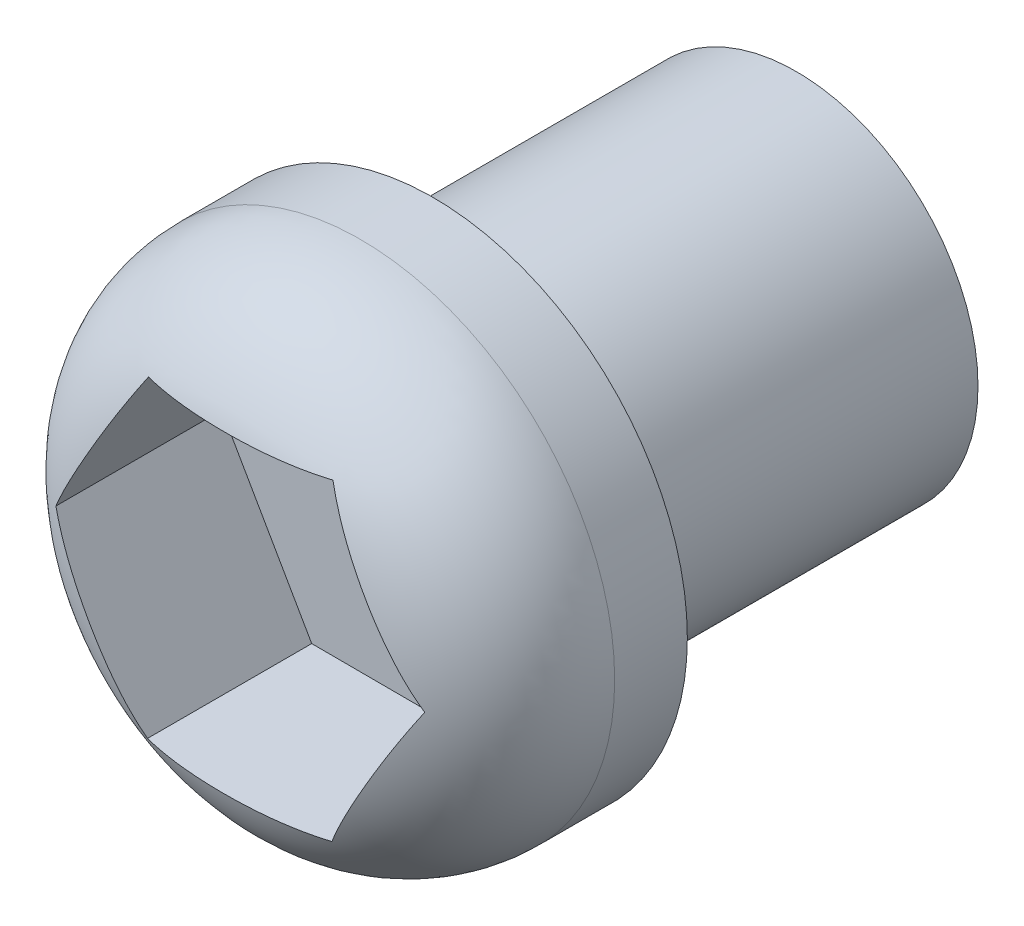
SolidWorks part; units mm, degrees
ref_plane "Front Plane" through (0, 0, 0) normal (0, 0, 1) x (1, 0, 0)
ref_plane "Top Plane" through (0, 0, 0) normal (0, 1, 0) x (1, 0, 0)
ref_plane "Right Plane" through (0, 0, 0) normal (1, 0, 0) x (0, 0, -1)
sketch "Sketch1" plane through (0, 0, 0) normal (0, 0, 1) x (1, 0, 0)
  circle A0 centre (-3.1842, -0.3489) radius 3.5
  dimension "D1" = 7
extrude "Boss-Extrude1" add sketch "Sketch1" along normal blind 3
sketch "Sketch2" plane through (0, 0, 0) normal (0, 0, -1) x (-1, 0, 0)
  circle A0 centre (3.1842, -0.3489) radius 2.5
  dimension "D1" = 5
extrude "Boss-Extrude2" add sketch "Sketch2" along normal blind 5
sketch "Sketch3" plane through (0, 0, 3) normal (0, 0, 1) x (1, 0, 0)
  line L1 (-4.3404, 1.8121) -> (-5.5926, -0.3413)
  line L2 (-5.5926, -0.3413) -> (-4.3537, -2.5024)
  line L3 (-4.3537, -2.5024) -> (-1.8627, -2.51)
  line L4 (-1.8627, -2.51) -> (-0.6106, -0.3566)
  line L5 (-0.6106, -0.3566) -> (-1.8494, 1.8045)
  line L6 (-1.8494, 1.8045) -> (-4.3404, 1.8121)
  circle A0 centre (-3.1016, -0.3489) radius 2.1573 construction
extrude "Cut-Extrude2" cut sketch "Sketch3" against normal blind 2.5 contours L5 L6 L1 L2 L3 L4
fillet "Fillet3" radius 2 1 edges at (0.3158, -0.3489, 3)
